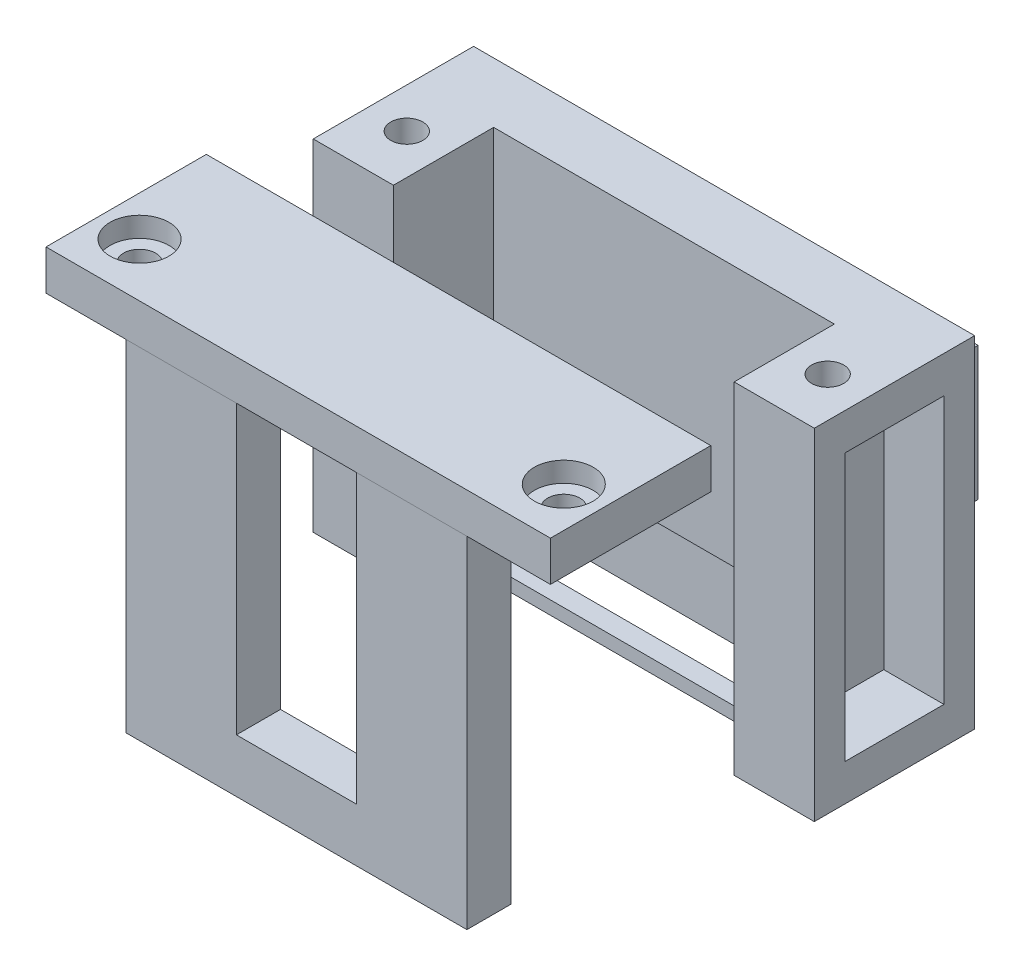
SolidWorks part; units mm, degrees
ref_plane "Front Plane" through (0, 0, 0) normal (0, 0, 1) x (1, 0, 0)
ref_plane "Top Plane" through (0, 0, 0) normal (0, 1, 0) x (1, 0, 0)
ref_plane "Right Plane" through (0, 0, 0) normal (1, 0, 0) x (0, 0, -1)
sketch "Sketch1" plane through (0, 0, 0) normal (0, 1, 0) x (1, 0, 0)
  line L0 (-12.75, -1) -> (12.75, -1)
  line L1 (-12.75, -2.5) -> (12.75, -2.5)
  line L2 (-12.75, -2.5) -> (-12.75, 2.5)
  line L3 (-12.75, 2.5) -> (12.75, 2.5)
  line L4 (12.75, -2.5) -> (12.75, 2.5)
  line L5 (-12.75, -2.5) -> (12.75, 2.5) construction
  line L6 (-12.75, 2.5) -> (12.75, -2.5) construction
  line L7 (0, 12.362) -> (0, -19.9667) construction
  line L8 (-12.75, 6) -> (-18.75, 6)
  line L9 (-12.75, 6) -> (-12.75, -6)
  line L10 (-12.75, -6) -> (-18.75, -6)
  line L11 (-18.75, 6) -> (-18.75, -6)
  line L12 (12.75, 0) -> (-12.75, 0) construction
  line L13 (-18.75, 0) -> (-12.75, 0) construction
  line L14 (12.75, -6) -> (18.75, -6)
  line L15 (12.75, 6) -> (18.75, 6)
  line L16 (18.75, 6) -> (18.75, -6)
  line L17 (12.75, 6) -> (12.75, -6)
  line L18 (-12.75, 6) -> (12.75, 6)
  point P0 (0, 0)
  dimension "D1" = 5
  dimension "D2" = 25.5
  dimension "D3" = 1.5
  dimension "D4" = 12
  dimension "D5" = 6
extrude "Boss-Extrude1" add sketch "Sketch1" along normal blind 24.5 contours L8 L11 L10 L9 L2 | L18 L9 L3 L17 | L15 L17 L4 L14 L16 region at (-15.75, 0, 0) region at (15.75, 0, 0) region at (0, 0, -4.25)
extrude "Boss-Extrude2" add sketch "Sketch1<3>" against normal blind 1 contours L1 L4 L0 L2 | L8 L11 L10 L9 L2 | L18 L9 L3 L17 | L15 L17 L4 L14 L16 region at (0, 0, 1.75) region at (-15.75, 0, 0) region at (15.75, 0, 0) region at (0, 0, -4.25)
sketch "Sketch1<3>" plane through (0, 0, 0) normal (0, 1, 0) x (1, 0, 0) same geometry as "Sketch1"
sketch "Sketch2" plane through (0, 24.5, 0) normal (0, 1, 0) x (1, 0, 0)
  line L0 (-18.75, 6) -> (-18.75, -6) construction
  line L1 (-12.75, -6) -> (-18.75, -6) construction
  line L2 (0, 6) -> (0, 2.5) construction
  line L3 (18.75, 6) -> (-18.75, 6) construction
  line L4 (-12.75, 2.5) -> (12.75, 2.5) construction
  circle A0 centre (-15.75, -2) radius 1.2
  circle A1 centre (15.75, -2) radius 1.2
  dimension "D1" = 2.4
  dimension "D2" = 3
  dimension "D3" = 4
extrude "Cut-Extrude1" cut sketch "Sketch2" against normal blind 14.5
sketch "Sketch3" plane through (-18.75, 0, 0) normal (-1, 0, 0) x (0, 0, 1)
  line L1 (-0.8, 10.55) -> (4.8, 10.55)
  line L2 (-0.8, 10.55) -> (-0.8, 12.45)
  line L3 (-0.8, 12.45) -> (4.8, 12.45)
  line L4 (4.8, 10.55) -> (4.8, 12.45)
  line L5 (-0.8, 11.5) -> (4.8, 11.5) construction
  line L6 (-6, 24.5) -> (6, 24.5) construction
  line L7 (2, 12.45) -> (2, 10.55) construction
  line L8 (6, 24.5) -> (6, -1) construction
  dimension "D1" = 1.9
  dimension "D2" = 5.6
  dimension "D3" = 13
  dimension "D4" = 4
sketch "Sketch5" plane through (18.75, 0, 0) normal (1, 0, 0) x (0, 0, -1)
  line L0 (0, 21.75) -> (0, 1.75) construction
  line L1 (-3.7, 1.75) -> (3.7, 1.75)
  line L2 (-3.7, 1.75) -> (-3.7, 21.75)
  line L3 (-3.7, 21.75) -> (3.7, 21.75)
  line L4 (3.7, 1.75) -> (3.7, 21.75)
  line L5 (0, 24.5) -> (0, -1) construction
  line L6 (6, 24.5) -> (-6, 24.5) construction
  line L7 (6, -1) -> (-6, -1) construction
  line L8 (-3.7, 11.75) -> (3.7, 11.75) construction
  line L9 (-6, 11.75) -> (6, 11.75) construction
  line L12 (-6, 24.5) -> (-6, -1) construction
  line L13 (6, 24.5) -> (6, -1) construction
  dimension "D1" = 20
  dimension "D2" = 7.4
  dimension "D3" = 7.4
  dimension "D4" = 12
extrude "Cut-Extrude3" cut sketch "Sketch5" against normal blind 4.5
sketch "Sketch6" plane through (0, 0, 6) normal (0, 0, 1) x (1, 0, 0)
  line L0 (12.75, 11.75) -> (18.75, 11.75) construction
  line L1 (12.75, 24.5) -> (12.75, -1) construction
  line L2 (18.75, 24.5) -> (18.75, -1) construction
  circle A0 centre (17.6, 4.75) radius 0.65
  circle A1 centre (17.6, 18.75) radius 0.65
  dimension "D1" = 1.3
  dimension "D2" = 7
  dimension "D3" = 1.15
sketch "Sketch7" plane through (0, 0, 6) normal (0, 0, 1) x (1, 0, 0)
  line L0 (0, 24.5) -> (0, -1) construction
  line L1 (-12.75, 24.5) -> (12.75, 24.5)
  line L2 (-12.75, 24.5) -> (-12.75, -1)
  line L3 (-12.75, -1) -> (12.75, -1)
  line L4 (12.75, 24.5) -> (12.75, -1)
  line L9 (-4.5, 15.5) -> (4.5, 15.5)
  line L10 (-4.5, 15.5) -> (-4.5, 3)
  line L11 (-4.5, 3) -> (4.5, 3)
  line L12 (4.5, 15.5) -> (4.5, 3)
  line L13 (0, 15.5) -> (0, 3) construction
  line L14 (-4.5, 15.5) -> (-4.5, 24.5)
  line L15 (-18.75, 24.5) -> (19, 24.5)
  line L16 (-18.75, 24.5) -> (-18.75, 27.5)
  line L17 (-18.75, 27.5) -> (19, 27.5)
  line L18 (19, 24.5) -> (19, 27.5)
  line L19 (4.5, 15.5) -> (4.5, 24.5)
  line M8 (-12.75, -1) -> (-12.75, 24.5)
  line M9 (-12.75, 24.5) -> (-18.75, 24.5)
  dimension "D1" = 4
  dimension "D2" = 9
  dimension "D3" = 9
  dimension "D4" = 3
extrude "Boss-Extrude3" add sketch "Sketch7" against normal blind 3.3 from offset 20 separate body contours L19 L12 L11 L10 L14 L1 L3 L4 L15 M8 region at (-8.625, 24.1394, 6)
extrude "Boss-Extrude4" add sketch "Sketch7<3>" against normal blind 12 from offset 20 separate body contours L15 L18 L17 L16 L1 M9 region at (0.125, 26, 6)
sketch "Sketch7<3>" plane through (0, 0, 6) normal (0, 0, 1) x (1, 0, 0) same geometry as "Sketch7"
sketch "Sketch8" plane through (0, 27.5, 0) normal (0, 1, 0) x (1, 0, 0)
  line L0 (-18.75, -14) -> (-18.75, -26) construction
  line L1 (-18.75, -26) -> (19, -26) construction
  line L2 (0.125, -14) -> (0.125, -26) construction
  line L3 (-18.75, -14) -> (19, -14) construction
  circle A0 centre (-15.75, -22) radius 1.2
  circle A1 centre (-15.75, -22) radius 2.2
  circle A2 centre (16, -22) radius 2.2
  circle A3 centre (16, -22) radius 1.2
  dimension "D1" = 2.4
  dimension "D4" = 4.4
  dimension "D2" = 3
  dimension "D3" = 4
extrude "Cut-Extrude5" cut sketch "Sketch8" against normal blind 1.5 contours A1 A0 | A2 A3 | A1 region at (-17.8878, 27.5, 22) region at (13.8622, 27.5, 22)
extrude "Cut-Extrude6" cut sketch "Sketch8<3>" against normal blind 3 contours A0 | A3 region at (-15.75, 27.5, 22) region at (16, 27.5, 22)
sketch "Sketch8<3>" plane through (0, 27.5, 0) normal (0, 1, 0) x (1, 0, 0) same geometry as "Sketch8"
extrude "Cut-Extrude7" cut sketch "Sketch5<2>" along normal blind 4.5 from surface starting at face at (-18.75, 11.75, 0)
sketch "Sketch5<2>" plane through (18.75, 0, 0) normal (1, 0, 0) x (0, 0, -1) same geometry as "Sketch5"
sketch "Sketch9" plane through (0, 0, -2.5) normal (0, 0, 1) x (1, 0, 0)
  line L0 (12.75, 24.5) -> (12.75, -1) construction
  line L1 (-12.75, 24.5) -> (12.75, 24.5)
  line L2 (-12.75, 24.5) -> (-12.75, 5)
  line L3 (-12.75, 5) -> (12.75, 5)
  line L4 (12.75, 24.5) -> (12.75, 5)
  line L5 (-12.75, -1) -> (12.75, -1) construction
  dimension "D1" = 6
extrude "Boss-Extrude5" add sketch "Sketch9" along normal blind 1
sketch "Sketch10" plane through (0, 0, -6) normal (0, 0, -1) x (-1, 0, 0)
  line L0 (-18.75, 11.75) -> (18.75, 11.75) construction
  line L1 (-18.75, 24.5) -> (-18.75, -1) construction
  line L2 (18.75, 24.5) -> (18.75, -1) construction
  line L3 (0, 24.5) -> (0, -1) construction
  line L4 (-18.75, 24.5) -> (18.75, 24.5) construction
  line L5 (-18.75, -1) -> (18.75, -1) construction
  line L6 (-4, 4) -> (4, 4) construction
  line L7 (-4, 9) -> (4, 9)
  line L8 (-4, 9) -> (-4, -1)
  line L9 (-4, -1) -> (4, -1)
  line L10 (4, 9) -> (4, -1)
  line L11 (0, 9) -> (0, -1) construction
  dimension "D1" = 10
  dimension "D2" = 8
extrude "Boss-Extrude6" add sketch "Sketch10" along normal blind 15
sketch "Sketch11" plane through (-4, 0, 0) normal (-1, 0, 0) x (0, 0, 1)
  line L0 (-21, 4) -> (-6, 4) construction
  line L1 (-21, -1) -> (-21, 9) construction
  line L2 (-6, -1) -> (-6, 9) construction
  line L3 (-16, 9) -> (-16, -1) construction
  line L4 (-21, 9) -> (-6, 9) construction
  line L5 (-21, -1) -> (-6, -1) construction
  circle A0 centre (-16, 4) radius 2.5
  dimension "D2" = 5
  dimension "D1" = 5
extrude "Cut-Extrude8" cut sketch "Sketch11" against normal through all
